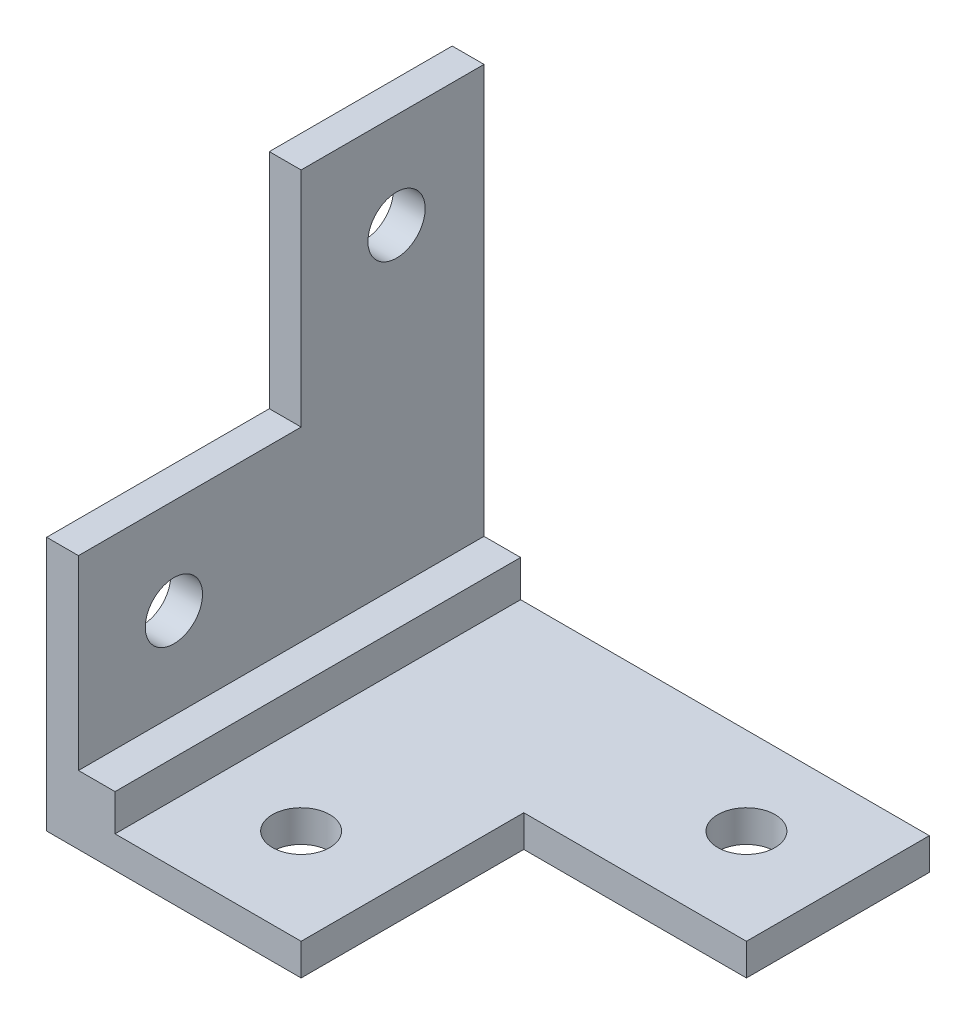
SolidWorks part; units mm, degrees
ref_plane "Front Plane" through (0, 0, 0) normal (0, 0, 1) x (1, 0, 0)
ref_plane "Top Plane" through (0, 0, 0) normal (0, 1, 0) x (1, 0, 0)
ref_plane "Right Plane" through (0, 0, 0) normal (1, 0, 0) x (0, 0, -1)
sketch "Sketch2" plane through (0, 0, 0) normal (0, 0, 1) x (1, 0, 0)
  line L1 (0, 0) -> (38.1, 0)
  line L2 (0, 0) -> (0, 38.1)
  line L3 (0, 38.1) -> (38.1, 38.1)
  line L4 (38.1, 0) -> (38.1, 38.1)
  dimension "D1" = 38.1
  dimension "D2" = 38.1
extrude "Boss-Extrude2" add sketch "Sketch2" along normal blind 38.1
sketch "Sketch3" plane through (0, 0, 38.1) normal (0, 0, 1) x (1, 0, 0)
  line L0 (0, 0) -> (38.1, 0) construction
  line L1 (38.1, 38.1) -> (2.54, 38.1)
  line L2 (38.1, 38.1) -> (38.1, 2.54)
  line L3 (38.1, 2.54) -> (2.54, 2.54)
  line L4 (2.54, 38.1) -> (2.54, 2.54)
  line L5 (0, 38.1) -> (0, 0) construction
  dimension "D1" = 2.54
  dimension "D2" = 2.54
extrude "Cut-Extrude1" cut sketch "Sketch3" against normal blind 35.56
sketch "Sketch4" plane through (0, 0, 2.54) normal (0, 0, 1) x (1, 0, 0)
  line L1 (38.1, 38.1) -> (20.32, 38.1)
  line L2 (38.1, 38.1) -> (38.1, 20.32)
  line L3 (38.1, 20.32) -> (20.32, 20.32)
  line L4 (20.32, 38.1) -> (20.32, 20.32)
  line L6 (38.1, 38.1) -> (2.54, 38.1) construction
  line L7 (38.1, 2.54) -> (38.1, 38.1) construction
  line L8 (2.54, 38.1) -> (2.54, 2.54) construction
  line L9 (2.54, 2.54) -> (38.1, 2.54) construction
  circle A0 centre (12.7, 30.48) radius 2.286
  circle A1 centre (30.48, 12.7) radius 2.286
  dimension "D4" = 7.62
  dimension "D5" = 4.572
  dimension "D1" = 17.78
  dimension "D2" = 17.78
  dimension "D3" = 7.62
  dimension "D6" = 7.62
  dimension "D7" = 7.62
extrude "Cut-Extrude2" cut sketch "Sketch4" against normal through all
sketch "Sketch5" plane through (0, 2.54, 0) normal (0, 1, 0) x (1, 0, 0)
  line L1 (38.1, -38.1) -> (20.32, -38.1)
  line L2 (38.1, -38.1) -> (38.1, -20.32)
  line L3 (38.1, -20.32) -> (20.32, -20.32)
  line L4 (20.32, -38.1) -> (20.32, -20.32)
  line L5 (2.54, -2.54) -> (2.54, -38.1) construction
  line L8 (38.1, -2.54) -> (38.1, -38.1) construction
  line L9 (2.54, -38.1) -> (38.1, -38.1) construction
  line L10 (2.54, -2.54) -> (38.1, -2.54) construction
  circle A0 centre (30.48, -12.7) radius 2.286
  circle A1 centre (12.7, -30.48) radius 2.286
  dimension "D1" = 4.572
  dimension "D2" = 7.62
  dimension "D3" = 7.62
  dimension "D4" = 17.78
  dimension "D5" = 17.78
  dimension "D6" = 7.62
  dimension "D7" = 7.62
extrude "Cut-Extrude3" cut sketch "Sketch5" against normal through all
sketch "Sketch6" plane through (2.54, 0, 0) normal (1, 0, 0) x (0, 0, -1)
  line L1 (-38.1, 38.1) -> (-20.32, 38.1)
  line L2 (-38.1, 38.1) -> (-38.1, 20.32)
  line L3 (-38.1, 20.32) -> (-20.32, 20.32)
  line L4 (-20.32, 38.1) -> (-20.32, 20.32)
  line L7 (-2.54, 38.1) -> (-2.54, 20.32) construction
  line L8 (-20.32, 2.54) -> (-38.1, 2.54) construction
  line L9 (-38.1, 38.1) -> (-38.1, 2.54) construction
  line L10 (-2.54, 38.1) -> (-38.1, 38.1) construction
  circle A0 centre (-12.7, 30.48) radius 2.286
  circle A1 centre (-30.48, 12.7) radius 2.286
  dimension "D1" = 4.572
  dimension "D2" = 17.78
  dimension "D3" = 17.78
  dimension "D4" = 7.62
  dimension "D5" = 7.62
  dimension "D6" = 7.62
  dimension "D7" = 7.62
extrude "Cut-Extrude4" cut sketch "Sketch6" against normal through all
sketch "Sketch7" plane through (0, 2.54, 0) normal (0, 1, 0) x (1, 0, 0)
  line L0 (2.54, -38.1) -> (2.54, -2.54)
  line L1 (2.54, -2.54) -> (38.1, -2.54)
  line L2 (38.1, -2.54) -> (38.1, -5.461)
  line L3 (38.1, -2.54) -> (38.1, -20.32) construction
  line L4 (38.1, -5.461) -> (5.461, -5.461)
  line L5 (5.461, -5.461) -> (5.461, -38.1)
  line L6 (2.54, -38.1) -> (20.32, -38.1) construction
  line L7 (5.461, -38.1) -> (2.54, -38.1)
  dimension "D1" = 2.921
  dimension "D2" = 2.921
extrude "Boss-Extrude3" add sketch "Sketch7" along normal blind 2.921
sketch "Sketch8" plane through (0, 5.461, 0) normal (0, 1, 0) x (1, 0, 0)
  line L1 (5.461, -5.461) -> (2.54, -5.461)
  line L2 (5.461, -5.461) -> (5.461, -2.54)
  line L3 (5.461, -2.54) -> (2.54, -2.54)
  line L4 (2.54, -5.461) -> (2.54, -2.54)
extrude "Boss-Extrude4" add sketch "Sketch8" along normal up to surface (32.639 mm away) up to face at (7.62, 38.1, 7.62)
sketch "Sketch12" plane through (38.1, 0, 0) normal (1, 0, 0) x (0, 0, -1)
  line L0 (0, 0) -> (-5.715, 0)
  line L2 (0, 0) -> (0, 38.1)
  line L5 (-20.32, 0) -> (0, 0) construction
  line L6 (-5.715, 0) -> (-5.715, 38.1)
  line L7 (-5.715, 38.1) -> (0, 38.1)
  dimension "D1" = 5.715
extrude "Cut-Extrude6" cut sketch "Sketch12" against normal through all
